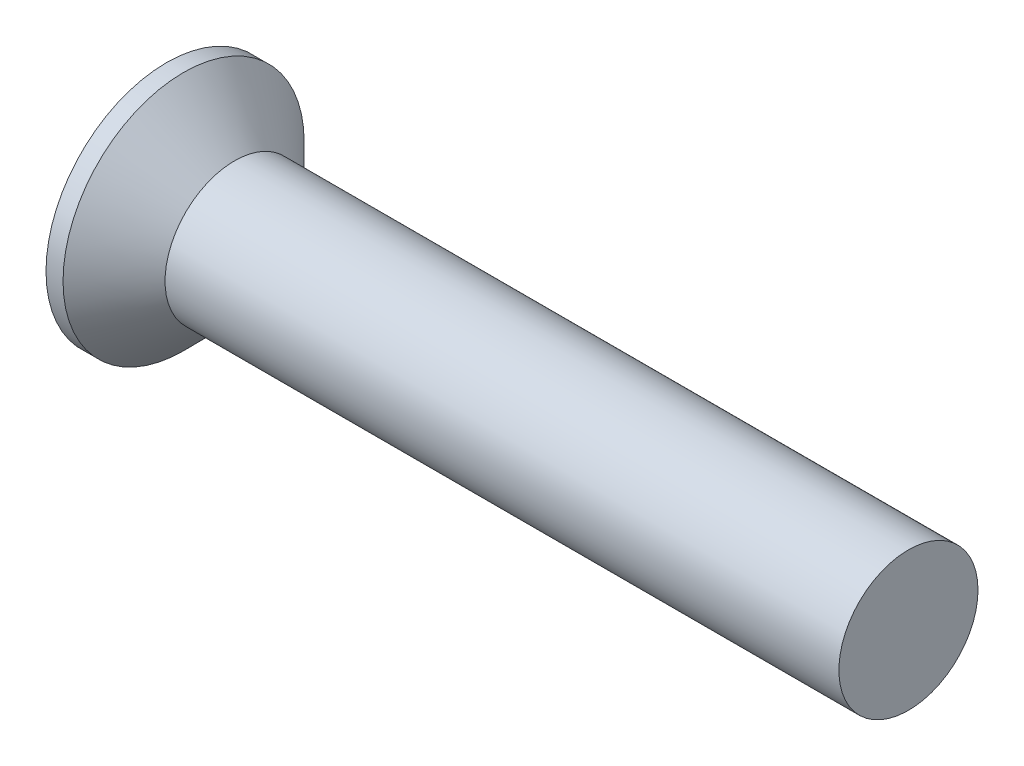
SolidWorks part; units mm, degrees
ref_plane "Front" through (0, 0, 0) normal (0, 0, 1) x (1, 0, 0)
ref_plane "Top" through (0, 0, 0) normal (0, 1, 0) x (1, 0, 0)
ref_plane "Right" through (0, 0, 0) normal (1, 0, 0) x (0, 0, -1)
sketch "Sketch1" plane through (0, 0, 0) normal (0, 0, 1) x (1, 0, 0)
  line L0 (16, 1.5) -> (2.7379, 1.5)
  line L1 (2.7379, 1.5) -> (2.4674, 1.2295) construction
  line L2 (1.65, 1.3174) -> (1.4674, 1.5) construction
  line L3 (0.3674, 2.6) -> (0, 2.6)
  line L4 (16, 1.5) -> (16, 0)
  line L5 (4.5158, 0) -> (-89.8219, 0) construction
  line L6 (16, 0) -> (0, 0)
  line L7 (0, 2.6) -> (0, 0)
  line L8 (1.8621, 1.2295) -> (2.4674, 1.2295) construction
  line L9 (2.7379, 1.5) -> (1.4674, 1.5)
  line L10 (1.4674, 1.5) -> (0.3674, 2.6)
  arc A0 (1.8621, 1.2295) -> (1.65, 1.3174) centre (1.8621, 1.5295) cw construction
  point P11 (1.7379, 1.2295)
  dimension "D1" = 45
  dimension "dk" = 5.2
  dimension "l" = 16
  dimension "a" = 1
  dimension "D3" = 45
  dimension "k" = 1.65
revolve "Base" add sketch "Sketch1" angle 360 about L5
cosmetic thread "ThreadCosmetic1" [suppressed] parameters "bb"=14.35
dome "BaseTop" faces to dome 1 distance 0.7 reverse direction no elliptical dome no face at (0, 0, -2.6) parameters "f"=0.7
ref_plane "Plane1" through (-0.7, 0, 0) normal (1, 0, 0) x (0, 0, -1)
sketch "Sketch6" plane through (-0.7, 0, 0) normal (-1, 0, 0) x (0, 0, 1)
  line L0 (-1.9271, 0) -> (2.0512, 0) construction
  line L1 (0, 1.8651) -> (0, -2.0207) construction
  line L2 (0.34, 0.34) -> (0.34, 1.7)
  line L3 (0.34, 1.7) -> (-0.34, 1.7)
  line L4 (-0.34, 0.34) -> (-0.34, 1.7)
  line L5 (0.34, 0.34) -> (1.7, 0.34)
  line L6 (1.7, 0.34) -> (1.7, -0.34)
  line L7 (-1.7, 0.34) -> (-1.7, -0.34)
  line L8 (-0.34, 0.34) -> (-1.7, 0.34)
  line L9 (-0.34, -0.34) -> (-1.7, -0.34)
  line L10 (0.34, -0.34) -> (1.7, -0.34)
  line L11 (-0.34, -0.34) -> (-0.34, -1.7)
  line L12 (0.34, -1.7) -> (-0.34, -1.7)
  line L13 (0.34, -0.34) -> (0.34, -1.7)
  point P16 (-1.7, 0)
  point P17 (1.7, 0)
extrude "CrossRecess" cut sketch "Sketch6" against normal blind 0.825
draft "Draft9" type of draft neutral plane draft angle 30 neutral plane "Plane1" faces to draft 4 face at (-0.141, 0, -1.7) face at (-0.141, -1.7, 0) face at (-0.141, 0, 1.7) face at (-0.141, 1.7, 0) neutral plane through (-0.7, 0, 0) neutral plane normal (1, 0, 0) reverse direction yes parameters "D1"=30
fillet "Fillet5" radius 0.3 4 edges at (-0.2763, -0.34, 0.34) (-0.2763, -0.34, -0.34) (-0.2763, 0.34, -0.34) (-0.2763, 0.34, 0.34)
sketch "Sketch7" plane through (-0.7, 0, 0) normal (-1, 0, 0) x (0, 0, 1)
  line L0 (-2.0126, 0) -> (1.9757, 0) construction
  line L1 (0, 1.9314) -> (0, -2.0126) construction
  line L2 (0, 0) -> (1.5555, 1.5555) construction
  line L3 (0, 0.5081) -> (1.2021, 1.2021)
  line L4 (-1.5402, 1.5402) -> (0, 0) construction
  line L5 (0.5081, 0) -> (1.2021, 1.2021)
  line L6 (0, -0.5081) -> (1.2021, -1.2021)
  line L7 (0.5081, 0) -> (1.2021, -1.2021)
  line L8 (-0.5081, 0) -> (-1.2021, -1.2021)
  line L9 (0, -0.5081) -> (-1.2021, -1.2021)
  line L10 (-0.5081, 0) -> (-1.2021, 1.2021)
  line L11 (0, 0.5081) -> (-1.2021, 1.2021)
  dimension "D3" = 15
extrude "Cut-Extrude3" [suppressed] cut sketch "Sketch7" against normal blind 10 draft 20
sketch "Sketch8" plane through (0, 0, 0) normal (0, 0, 1) x (1, 0, 0)
  line L0 (-9, 1.5) -> (-10.25, 1.2295)
  line L1 (-10.25, 1.2295) -> (1.7379, 1.2295)
  line L3 (16, -1.5) -> (16, 1.5) construction
  line L4 (1.8621, 1.2295) -> (2.4674, 1.2295) construction
  line L5 (1.8458, 1.1216) -> (1.7379, 1.2295)
  line L6 (1.8458, 1.1216) -> (1.8458, 6.2295)
  line L7 (1.8458, 6.2295) -> (-9, 6.2295)
  line L8 (-9, 6.2295) -> (-9, 1.5)
  line L9 (62.4753, 0) -> (52.9594, 0) construction
  line L10 (1.65, 1.3174) -> (1.4674, 1.5) construction
  dimension "D1" = 5
  dimension "x" = 1.25
sketch "Sketch9" plane through (0, 0, 0) normal (0, 0, 1) x (1, 0, 0)
  line L0 (16, 1.2657) -> (16.1352, 1.5)
  line L1 (16.1352, 1.5) -> (16.1352, 1.7705)
  line L2 (16.1352, 1.7705) -> (15.8648, 1.7705)
  line L3 (15.8648, 1.7705) -> (15.8648, 1.5)
  line L4 (15.8648, 1.5) -> (16, 1.2657)
  line L5 (16, -1.5) -> (16, 1.5) construction
  line L6 (0, 0) -> (66.6901, 0) construction
  dimension "D1" = 3
  dimension "D2" = 0.2705
revolve "Cut-Revolve10" [suppressed] cut sketch "Sketch9" angle 360 about L6
pattern_linear "LPattern10" [suppressed] count 44 spacing 0.3246 along (-1, 0, 0) of bodies 105
equation "\"D1@Sketch6\" = \"m@Sketch6\" / 5"
equation "\"D1@CrossRecess\" = \"k@Sketch1\" / 2"
equation "\"D1@Plane1\" = \"f@BaseTop\""
equation "\"D1@Sketch9\" = \"d@Sketch1\""
equation "\"D2@Sketch9\" =  ( \"d@Sketch1\" - \"THD_MINOR@ThreadCosmetic1\" )  / 2"
equation "\"D3@LPattern10\" = \"D2@Sketch9\" * 1.2"
equation "\"D1@LPattern10\" = \"bb@ThreadCosmetic1\" / \"D3@LPattern10\" "
